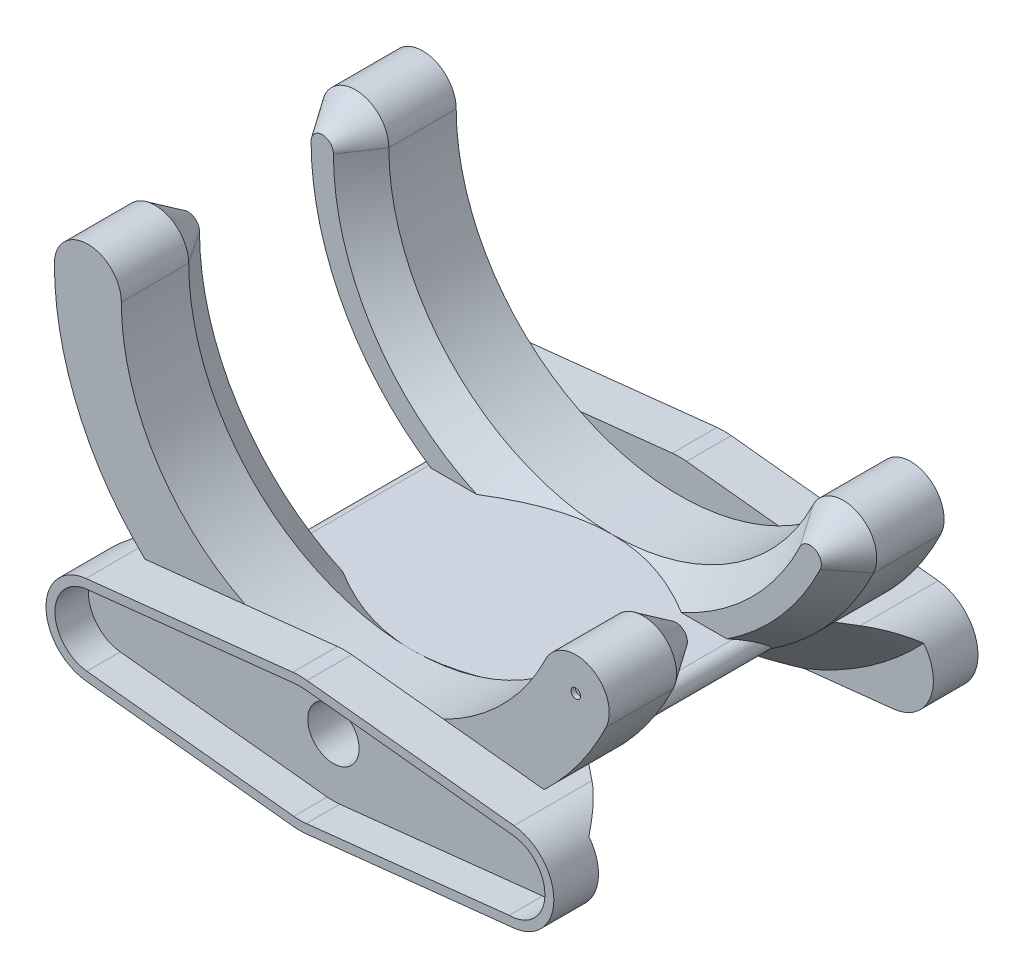
SolidWorks part; units mm, degrees
ref_plane "Front Plane" through (0, 0, 0) normal (0, 0, 1) x (1, 0, 0)
ref_plane "Top Plane" through (0, 0, 0) normal (0, 1, 0) x (1, 0, 0)
ref_plane "Right Plane" through (0, 0, 0) normal (1, 0, 0) x (0, 0, -1)
sketch "Sketch1" plane through (0, 0, 0) normal (0, 0, 1) x (1, 0, 0)
  line L1 (0, -12.7) -> (0, -20.32) construction
  arc A2 (-25.4, 12.7) -> (22.8736, 1.6565) centre (0, 12.7) ccw
  arc A3 (-33.02, 12.7) -> (29.7357, -1.6565) centre (0, 12.7) ccw
  arc A7 (-25.4, 12.7) -> (-33.02, 12.7) centre (-29.21, 12.7) ccw
  arc A9 (29.7357, -1.6565) -> (22.8736, 1.6565) centre (26.3046, 0) ccw
  point P11 (0, -12.7)
  point P13 (0, 0)
  point P15 (0, -20.32)
  dimension "D2" = 90
  dimension "D3" = 33.02
  dimension "D6" = 25.4
  dimension "D1" = 90
  dimension "D5" = 12.7
extrude "arm extrude" add sketch "Sketch1" along normal blind 38.1
sketch "Sketch2" plane through (0, 0, 38.1) normal (0, 0, 1) x (1, 0, 0)
  circle A1 centre (26.3046, 0) radius 0.5463
  arc A3 (29.7357, -1.6565) -> (22.8736, 1.6565) centre (26.3046, 0) ccw construction
extrude "guide hole" cut sketch "Sketch2" against normal blind 0.508
ref_plane "Plane1" through (0, 0, 19.05) normal (0, 0, 1) x (1, 0, 0)
mirror "Mirror1" about plane through (0, 0, 19.05) normal (0, 0, 1) of "guide hole"
sketch "Sketch4" plane through (0, 0, 0) normal (1, 0, 0) x (0, 0, -1)
  line L1 (-26.67, 28.1064) -> (-11.43, 28.1064)
  line L2 (-26.67, 28.1064) -> (-26.67, -12.7)
  line L3 (-26.67, -12.7) -> (-11.43, -12.7)
  line L4 (-11.43, 28.1064) -> (-11.43, -12.7)
  line L6 (-38.1, -12.7) -> (0, -12.7) construction
  point P4 (-19.05, 28.1064)
  dimension "D1" = 15.24
extrude "mid cut" cut sketch "Sketch4" against normal through all and the other way through all contours L2 L3 L4 L1
chamfer "Chamfer1" distance 2.54 angle 56 6 edges at (-29.8915, -1.3292, 26.67) (26.0101, -7.6419, 26.67) (13.5029, -8.8135, 26.67) (-17.9605, -5.2605, 26.67) (-29.21, 16.51, 26.67) (27.9612, 3.431, 26.67) first distance on face at (-21.9029, -0.6949, 26.67) first distance on face at (19.5059, -6.4311, 26.67)
sketch "Sketch5" plane through (0, 0, 38.1) normal (0, 0, 1) x (1, 0, 0)
  line L0 (0, -12.7) -> (0, -20.32) construction
  line L1 (-24.3544, -11.459) -> (-0.8128, -8.9335)
  line L2 (0.8128, -8.9335) -> (24.3544, -11.459)
  line L3 (24.3544, -21.561) -> (0.8128, -24.0865)
  line L4 (-24.3544, -21.561) -> (-0.8128, -24.0865)
  line L5 (-23.8125, -16.51) -> (23.8125, -16.51) construction
  arc A0 (-33.02, 12.7) -> (29.7357, -1.6565) centre (0, 12.7) ccw construction
  arc A1 (-0.8128, -24.0865) -> (0.8128, -24.0865) centre (0, -16.51) ccw
  arc A2 (-24.3544, -11.459) -> (-24.3544, -21.561) centre (-23.8125, -16.51) ccw
  arc A3 (24.3544, -21.561) -> (24.3544, -11.459) centre (23.8125, -16.51) ccw
  arc A4 (0.8128, -8.9335) -> (-0.8128, -8.9335) centre (0, -16.51) ccw
  point P0 (0, -12.7)
  point P1 (0, -20.32)
  point P22 (0, -16.51)
  dimension "D3" = 15.24
  dimension "D4" = 10.16
  dimension "D1" = 47.625
extrude "servo horn base" add sketch "Sketch5" along normal blind 1.27
sketch "Sketch6" plane through (0, 0, 39.37) normal (0, 0, 1) x (1, 0, 0)
  line L0 (-23.8125, -16.51) -> (23.8125, -16.51) construction
  line L1 (-24.246, -12.4692) -> (-0.7044, -9.9437)
  line L2 (0.7044, -9.9437) -> (24.246, -12.4692)
  line L3 (23.8125, -20.574) -> (0.711, -23.0756)
  line L4 (-24.246, -20.5508) -> (-0.7044, -23.0763)
  line L30 (24.3544, -11.459) -> (0.8128, -8.9335)
  line L31 (0.8128, -24.0865) -> (24.3544, -21.561)
  line L32 (-24.3544, -21.561) -> (-0.8128, -24.0865)
  line L33 (-0.8128, -8.9335) -> (-24.3544, -11.459)
  line L34 (24.3544, -11.459) -> (0.8128, -8.9335)
  line L35 (0.8128, -24.0865) -> (24.3544, -21.561)
  line L36 (-24.3544, -21.561) -> (-0.8128, -24.0865)
  line L37 (-0.8128, -8.9335) -> (-24.3544, -11.459)
  arc A0 (0.8128, -8.9335) -> (-0.8128, -8.9335) centre (0, -16.51) ccw construction
  arc A1 (-0.7044, -23.0763) -> (0.711, -23.0756) centre (0, -16.51) ccw
  arc A2 (-24.246, -12.4692) -> (-24.246, -20.5508) centre (-23.8125, -16.51) ccw
  arc A3 (23.8125, -20.574) -> (24.246, -12.4692) centre (23.8125, -16.51) ccw
  arc A4 (24.3544, -21.561) -> (24.3544, -11.459) centre (23.8125, -16.51) ccw construction
  arc A5 (0.7044, -9.9437) -> (-0.7044, -9.9437) centre (0, -16.51) ccw
  arc A25 (24.3544, -21.561) -> (24.3544, -11.459) centre (23.8125, -16.51) ccw
  arc A26 (0.8128, -8.9335) -> (-0.8128, -8.9335) centre (0, -16.51) ccw
  arc A27 (-0.8128, -24.0865) -> (0.8128, -24.0865) centre (0, -16.51) ccw
  arc A28 (-24.3544, -11.459) -> (-24.3544, -21.561) centre (-23.8125, -16.51) ccw
  arc A29 (24.3544, -21.561) -> (24.3544, -11.459) centre (23.8125, -16.51) ccw
  arc A30 (0.8128, -8.9335) -> (-0.8128, -8.9335) centre (0, -16.51) ccw
  arc A31 (-0.8128, -24.0865) -> (0.8128, -24.0865) centre (0, -16.51) ccw
  arc A32 (-24.3544, -11.459) -> (-24.3544, -21.561) centre (-23.8125, -16.51) ccw
  point P0 (0, -8.89)
  dimension "D1" = 8.128
  dimension "D2" = 13.208
  dimension "D3" = 0
extrude "servo horn extrude" add sketch "Sketch6" along normal blind 3.81
fillet "Fillet1" radius 1.27 2 edges at (21.0988, -12.7, 20.9329) (-21.0988, -12.7, 20.9329)
chamfer "Chamfer2" distance 5.08 angle 45 1 edges at (0, -20.32, 38.1)
sketch "Sketch7" plane through (0, 0, 39.37) normal (0, 0, 1) x (1, 0, 0)
  circle A0 centre (0, -16.51) radius 2.921
  arc A1 (0.7044, -9.9437) -> (-0.7044, -9.9437) centre (0, -16.51) ccw construction
  dimension "D1" = 5.842
extrude "screwdriver hole" cut sketch "Sketch7" against normal through all
sketch "Sketch8" plane through (0, 0, 0) normal (0, 0, -1) x (-1, 0, 0)
  line L1 (-43.3229, 32.8392) -> (42.3138, 32.8392)
  line L2 (-43.3229, 32.8392) -> (-43.3229, -33.1665)
  line L3 (-43.3229, -33.1665) -> (42.3138, -33.1665)
  line L4 (42.3138, 32.8392) -> (42.3138, -33.1665)
ref_plane "Plane2" through (0, 0, 19.05) normal (0, 0, -1) x (-1, 0, 0)
extrude "Cut-Extrude1" cut sketch "Sketch8" against normal up to surface (19.05 mm away) contours L1 L4 L3 L2 up to plane "Plane2"
mirror "Mirror2" about plane through (0, 0, 19.05) normal (0, 0, -1) of bodies 108
